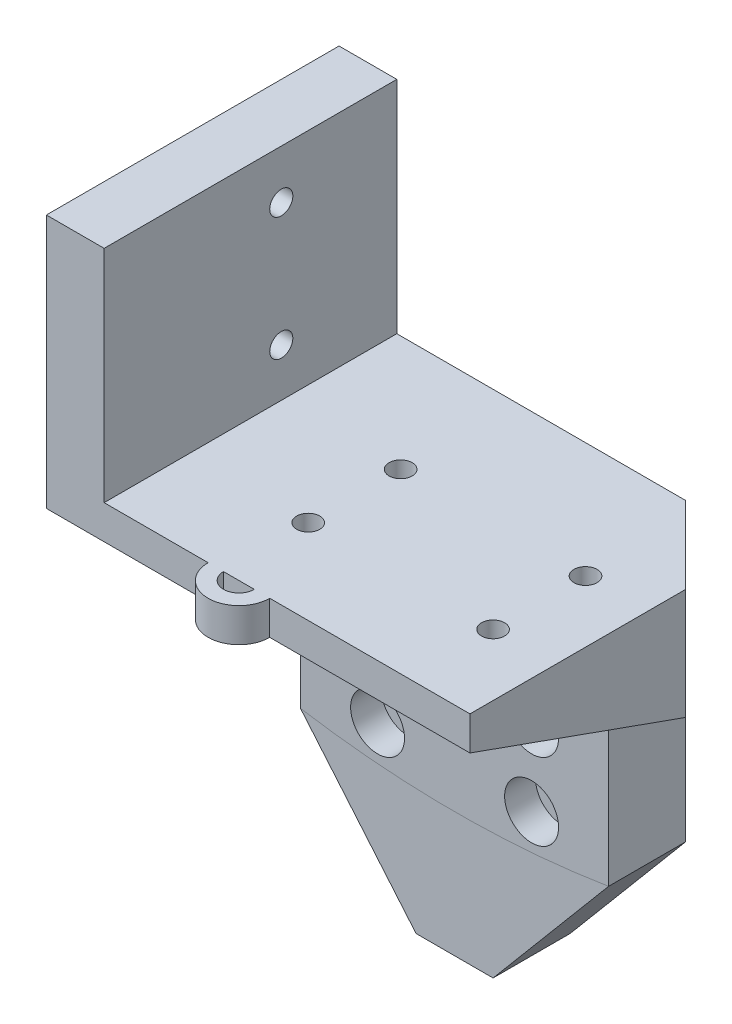
SolidWorks part; units mm, degrees
ref_plane "Plan de face" through (0, 0, 0) normal (0, 0, 1) x (1, 0, 0)
ref_plane "Plan de dessus" through (0, 0, 0) normal (0, 1, 0) x (1, 0, 0)
ref_plane "Plan de droite" through (0, 0, 0) normal (1, 0, 0) x (0, 0, -1)
sketch "Esquisse1" plane through (0, 0, 0) normal (0, 0, 1) x (1, 0, 0)
  line L0 (-20, -123.3896) -> (-20, -99.4)
  line L1 (-20, -99.4) -> (20, -99.4)
  line L2 (20, -99.4) -> (20, -123.3896)
  arc A0 (20, -123.3896) -> (-20, -123.3896) centre (0, 0) cw
  point P4 (0, -125)
  dimension "D1" = 125
  dimension "D3" = 25.6
  dimension "D2" = 40
extrude "Boss.-Extru.1" add sketch "Esquisse1" along normal blind 10
sketch "Esquisse2" plane through (0, 0, 10) normal (0, 0, 1) x (1, 0, 0)
  line L0 (0, -99.4) -> (0, -125) construction
  line L1 (20, -99.4) -> (-20, -99.4) construction
  line L2 (-10, -110) -> (-10, -120) construction
  line L3 (-10, -120) -> (10, -120) construction
  arc A0 (-20, -123.3896) -> (20, -123.3896) centre (0, 0) ccw construction
  circle A1 centre (-10, -110) radius 1.75
  circle A2 centre (-10, -120) radius 1.75
  circle A3 centre (10, -110) radius 1.75
  circle A4 centre (10, -120) radius 1.75
  point P16 (0, -112.2)
  point P17 (0, -120)
  dimension "D3" = 3.5
  dimension "D1" = 10
  dimension "D2" = 20
  dimension "D4" = 120
extrude "Enlèv. mat.-Extru.1" cut sketch "Esquisse2" against normal up to next
sketch "Esquisse4" plane through (0, 0, 10) normal (0, 0, 1) x (1, 0, 0)
  circle A0 centre (-10, -110) radius 3.5
  circle A1 centre (10, -110) radius 3.5
  circle A2 centre (10, -120) radius 3.5
  circle A3 centre (-10, -120) radius 3.5
  dimension "D1" = 7
extrude "Enlèv. mat.-Extru.2" cut sketch "Esquisse4" against normal blind 4
sketch "Esquisse5" plane through (0, -99.4, 0) normal (0, 1, 0) x (1, 0, 0)
  line L1 (-20, 0) -> (30, 0)
  line L2 (-20, 0) -> (-20, -38)
  line L3 (-20, -38) -> (30, -38)
  line L4 (30, 0) -> (30, -38)
  dimension "D1" = 50
  dimension "D2" = 38
extrude "Boss.-Extru.2" add sketch "Esquisse5" along normal blind 14.4
sketch "Esquisse6" plane through (0, -99.4, 0) normal (0, -1, 0) x (1, 0, 0)
  line L0 (20, 10) -> (-20, 10) construction
  line L1 (30, 38) -> (30, 0) construction
  circle A0 centre (-2, 27) radius 1.5
  circle A1 centre (22, 27) radius 1.5
  circle A2 centre (-2, 15) radius 1.5
  circle A3 centre (22, 15) radius 1.5
  dimension "D1" = 3
  dimension "D2" = 5
  dimension "D3" = 24
  dimension "D4" = 12
  dimension "D5" = 8
extrude "Enlèv. mat.-Extru.3" cut sketch "Esquisse6" against normal up to next
sketch "Esquisse7" plane through (0, -99.4, 0) normal (0, -1, 0) x (1, 0, 0)
  circle A0 centre (-2, 27) radius 3
  circle A1 centre (22, 27) radius 3
  circle A2 centre (22, 15) radius 3
  circle A3 centre (-2, 15) radius 3
  dimension "D1" = 6
extrude "Enlèv. mat.-Extru.4" cut sketch "Esquisse7" against normal offset from surface (9.4 mm away) 5 up to face at (22, -85, 28.5)
chamfer "Chanfrein1" distance 10 angle 45 1 edges at (30, -92.2, 0)
chamfer "Chanfrein2" distance 28 distance2 10 1 edges at (5, -99.4, 38) first distance on face at (-2, -99.4, 12)
sketch "Esquisse8" plane through (-20, 0, 0) normal (-1, 0, 0) x (0, 0, 1)
  line L0 (10, -99.4) -> (0, -99.4)
  line L1 (0, -85) -> (0, -123.3896) construction
  line L2 (0, -99.4) -> (0, -56.4)
  line L3 (0, -56.4) -> (38, -56.4)
  line L4 (38, -56.4) -> (38, -89.4)
  line L5 (38, -89.4) -> (10, -99.4)
  dimension "D1" = 43
extrude "Boss.-Extru.3" add sketch "Esquisse8" along normal blind 5
sketch "Esquisse9" plane through (-20, 0, 0) normal (1, 0, 0) x (0, 0, -1)
  line L4 (-38, -85) -> (0, -85)
  line L5 (0, -85) -> (0, -56.4)
  line L6 (0, -56.4) -> (-38, -56.4)
  line L7 (-38, -56.4) -> (-38, -85)
  line L8 (-38, -85) -> (0, -85)
  line L9 (0, -85) -> (0, -56.4)
  line L10 (0, -56.4) -> (-38, -56.4)
  line L11 (-38, -56.4) -> (-38, -85)
  dimension "D1" = 0
extrude "Boss.-Extru.4" add sketch "Esquisse9" along normal blind 2.5
chamfer "Chanfrein3" distance 5 angle 45 1 edges at (-20, -99.4, 5)
sketch "Esquisse10" plane through (-25, 0, 0) normal (-1, 0, 0) x (0, 0, 1)
  line L0 (38, -56.4) -> (0, -56.4) construction
  line L2 (13.5, -90) -> (16.5, -90) construction
  line L3 (13.5, -90) -> (16.5, -90) construction
  circle A0 centre (15, -62.75) radius 1.5
  circle A1 centre (15, -78.75) radius 1.5
  point P7 (15, -90)
  dimension "D1" = 3
  dimension "D2" = 16
  dimension "D3" = 6.35
extrude "Enlèv. mat.-Extru.5" cut sketch "Esquisse10" against normal up to next
sketch "Esquisse11" plane through (-25, 0, 0) normal (-1, 0, 0) x (0, 0, 1)
  circle A0 centre (15, -62.75) radius 3
  circle A1 centre (15, -78.75) radius 3
  dimension "D1" = 6
extrude "Enlèv. mat.-Extru.6" cut sketch "Esquisse11" against normal offset from surface (2.5 mm away) 5 up to face at (-17.5, -61.25, 15)
sketch "Esquisse12" plane through (0, 0, 10) normal (0, 0, 1) x (1, 0, 0)
  line L0 (0, 0) -> (0, -125) construction
  line L1 (0, -125) -> (0, -141.2) construction
  line L2 (-5, -141.2) -> (5, -141.2)
  line L3 (-5, -141.2) -> (-20, -123.3896)
  line L4 (20, -123.3896) -> (5, -141.2)
  arc A0 (-20, -123.3896) -> (20, -123.3896) centre (0, 0) ccw construction
  arc A1 (-20, -123.3896) -> (20, -123.3896) centre (0, 0) ccw
  point P9 (0, -141.2)
  dimension "D1" = 141.2
  dimension "D2" = 10
extrude "Boss.-Extru.5" add sketch "Esquisse12" against normal blind 10 separate body
sketch "Esquisse14" plane through (0, -141.2, 0) normal (0, -1, 0) x (1, 0, 0)
  line L0 (-5, 10) -> (5, 0) construction
  line L1 (-5, 0) -> (-5, 10) construction
  line L2 (-5, 10) -> (5, 10) construction
  circle A0 centre (0, 5) radius 2.75
  dimension "D1" = 5.5
extrude "Enlèv. mat.-Extru.7" cut sketch "Esquisse14" against normal blind 2
sketch "Esquisse15" plane through (0, -85, 0) normal (0, 1, 0) x (1, 0, 0)
  line L0 (-20, -10) -> (20, -10) construction
  line L1 (-20, -10) -> (20, -10) construction
  line L2 (-17.5, -38) -> (30, -38) construction
  line L3 (4, -38) -> (2, -38)
  line L4 (-2, -38) -> (-4, -38)
  arc A0 (-4, -38) -> (4, -38) centre (0, -38) ccw
  arc A1 (-2, -38) -> (2, -38) centre (0, -38) ccw
  point P9 (0, 0)
  point P10 (0, -10)
  dimension "D1" = 2
  dimension "D2" = 2
extrude "Boss.-Extru.6" add sketch "Esquisse15" against normal up to vertex (4.4 mm away) up to point (-25, -89.4, 38)
